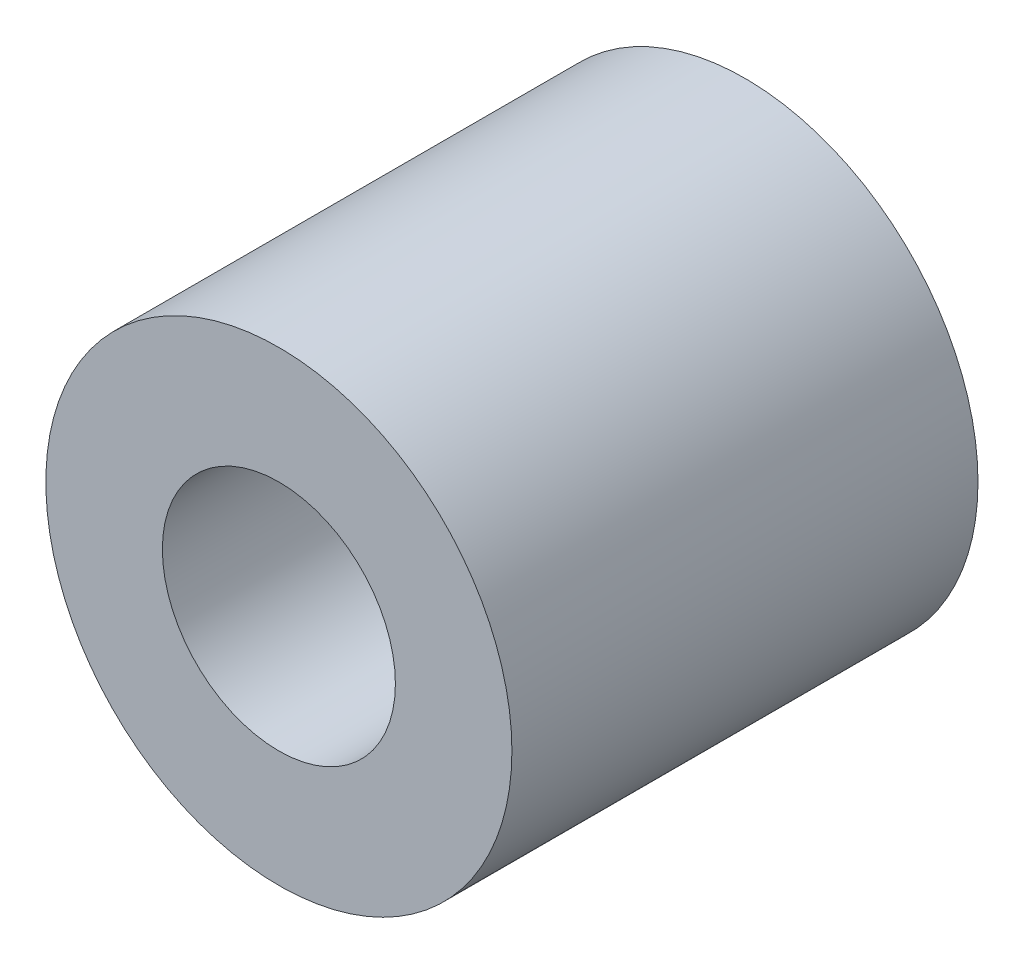
SolidWorks part; units mm, degrees
ref_plane "前视基准面" through (0, 0, 0) normal (0, 0, 1) x (1, 0, 0)
ref_plane "上视基准面" through (0, 0, 0) normal (0, 1, 0) x (1, 0, 0)
ref_plane "右视基准面" through (0, 0, 0) normal (1, 0, 0) x (0, 0, -1)
sketch "草图1" plane through (0, 0, 0) normal (0, 0, 1) x (1, 0, 0)
  circle A0 centre (0, 0) radius 1
  circle A1 centre (0, 0) radius 2
extrude "凸台-拉伸2" add sketch "草图1" along normal blind 4
